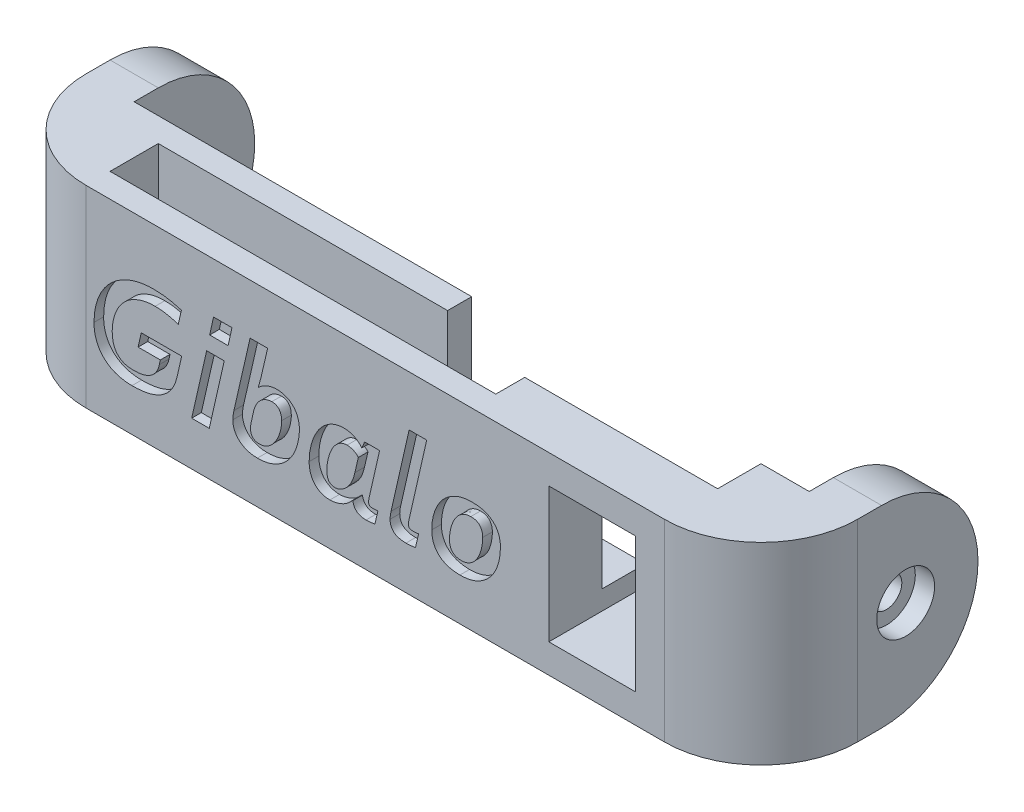
SolidWorks part; units mm, degrees
ref_plane "Front Plane" through (0, 0, 0) normal (0, 0, 1) x (1, 0, 0)
ref_plane "Top Plane" through (0, 0, 0) normal (0, 1, 0) x (1, 0, 0)
ref_plane "Right Plane" through (0, 0, 0) normal (1, 0, 0) x (0, 0, -1)
sketch "Sketch1" plane through (0, 0, 0) normal (0, 1, 0) x (1, 0, 0)
  line L1 (-34.0248, 5.3096) -> (35.9752, 5.3096)
  line L2 (-34.0248, 5.3096) -> (-34.0248, -4.6904)
  line L3 (-34.0248, -4.6904) -> (35.9752, -4.6904)
  line L4 (35.9752, 5.3096) -> (35.9752, -4.6904)
  line L5 (-34.0248, -4.6904) -> (-39.0248, -4.6904)
  line L6 (-34.0248, -4.6904) -> (-34.0248, 17.8096)
  line L7 (-34.0248, 17.8096) -> (-39.0248, 17.8096)
  line L8 (-39.0248, -4.6904) -> (-39.0248, 17.8096)
  line L9 (35.9752, -4.6904) -> (40.9752, -4.6904)
  line L10 (35.9752, -4.6904) -> (35.9752, 17.8096)
  line L11 (35.9752, 17.8096) -> (40.9752, 17.8096)
  line L12 (40.9752, -4.6904) -> (40.9752, 17.8096)
  dimension "D1" = 70
  dimension "D2" = 10
  dimension "D3" = 5
  dimension "D4" = 5
  dimension "D5" = 22.5
  dimension "D6" = 22.5
extrude "Boss-Extrude1" add sketch "Sketch1" along normal blind 20 contours L8 L5 L2 L6 L7 | L4 L1 L2 L3 | L9 L12 L11 L10 L4 region at (0.9752, 0, -0.3096) region at (-36.5248, 0, -6.5596) region at (38.4752, 0, -6.5596)
fillet "Fillet1" radius 10 2 edges at (40.9752, 10, 4.6904) (-39.0248, 10, 4.6904)
fillet "Fillet2" radius 10 4 edges at (-36.5248, 0, -17.8096) (38.4752, 0, -17.8096) (38.4752, 20, -17.8096) (-36.5248, 20, -17.8096)
sketch "Sketch4" plane through (40.9752, 0, 0) normal (1, 0, 0) x (0, 0, -1)
  line L0 (5.3096, 20) -> (7.8096, 20) construction
  line L1 (15.3096, 15) -> (15.3096, 5) construction
  circle A0 centre (10.3096, 10) radius 1.6
  dimension "D3" = 3.2
  dimension "D1" = 10
  dimension "D2" = 5
extrude "Cut-Extrude2" cut sketch "Sketch4" against normal blind 94
sketch "Sketch5" plane through (-39.0248, 0, 0) normal (-1, 0, 0) x (0, 0, 1)
  circle A0 centre (-10.3096, 10) radius 3
  dimension "D1" = 6
extrude "Cut-Extrude3" cut sketch "Sketch5" against normal blind 2
sketch "Sketch6" plane through (40.9752, 0, 0) normal (1, 0, 0) x (0, 0, -1)
  circle A0 centre (10.3096, 10) radius 3
  dimension "D1" = 6
extrude "Cut-Extrude4" cut sketch "Sketch6" against normal blind 2
sketch "Sketch7" plane through (0, 20, 0) normal (0, 1, 0) x (1, 0, 0)
  line L0 (-34.0248, 5.3096) -> (35.9752, 5.3096) construction
  line L1 (-29.0248, 2.8096) -> (10.9752, 2.8096)
  line L2 (-29.0248, 2.8096) -> (-29.0248, -2.1904)
  line L3 (-29.0248, -2.1904) -> (10.9752, -2.1904)
  line L4 (10.9752, 2.8096) -> (10.9752, -2.1904)
  line L5 (10.9752, -2.1904) -> (0.9752, -2.1904)
  line L6 (10.9752, -2.1904) -> (10.9752, 5.3096)
  line L7 (10.9752, 5.3096) -> (0.9752, 5.3096)
  line L8 (0.9752, -2.1904) -> (0.9752, 5.3096)
  line L9 (30.9752, -4.6904) -> (-29.0248, -4.6904) construction
  line L11 (10.9752, -2.1904) -> (30.9752, -2.1904)
  line L12 (10.9752, -2.1904) -> (10.9752, 5.3096)
  line L13 (10.9752, 5.3096) -> (30.9752, 5.3096)
  line L14 (30.9752, -2.1904) -> (30.9752, 5.3096)
  line L15 (10.9752, -2.1904) -> (30.9752, -2.1904)
  line L16 (10.9752, -2.1904) -> (10.9752, 0.8096)
  line L17 (10.9752, 0.8096) -> (30.9752, 0.8096)
  line L18 (30.9752, -2.1904) -> (30.9752, 0.8096)
  line M4 (35.9752, 5.3096) -> (-34.0248, 5.3096)
  dimension "D1" = 40
  dimension "D2" = 5
  dimension "D3" = 10
  dimension "D4" = 25
  dimension "D5" = 2.5
  dimension "D6" = 20
  dimension "D7" = 3
extrude "Cut-Extrude5" cut sketch "Sketch7" against normal blind 15 contours L3 L8 L1 L2 | L8 L3 L4 L1 | L8 L1 L6 M4 | L11 L14 L6 L4 M4 region at (-14.0248, 20, -0.3096) region at (5.9752, 20, -4.0596) region at (5.9752, 20, -0.3096) region at (20.9752, 20, -3.0596)
sketch "Sketch9" plane through (0, 0, 4.6904) normal (0, 0, 1) x (1, 0, 0)
  text T0 "<b>Gibalo</b>" font "Corbel" height in points 36
  point P1 (-28.5151, 4.5655)
  point P2 (-33.1172, 4.1453)
  point P3 (-30.7235, 4.5289)
  point P4 (0, 0)
  point P5 (-29.1545, 4.5653)
  point P6 (0, 0)
  point P7 (0, 0)
extrude "Cut-Extrude7" cut sketch "Sketch9" against normal offset from surface (1 mm away) 1 up to face at (0.9752, 10, 4.6904)
sketch "Sketch10" plane through (0, 0, 4.6904) normal (0, 0, 1) x (1, 0, 0)
  line L0 (30.9752, 20) -> (-29.0248, 20) construction
  line L1 (18.9752, 17) -> (27.9752, 17)
  line L2 (18.9752, 17) -> (18.9752, 3)
  line L3 (18.9752, 3) -> (27.9752, 3)
  line L4 (27.9752, 17) -> (27.9752, 3)
  line L6 (30.9752, 0) -> (30.9752, 20) construction
  dimension "D1" = 9
  dimension "D2" = 14
  dimension "D3" = 3
  dimension "D4" = 3
extrude "Cut-Extrude8" cut sketch "Sketch10" against normal blind 16
